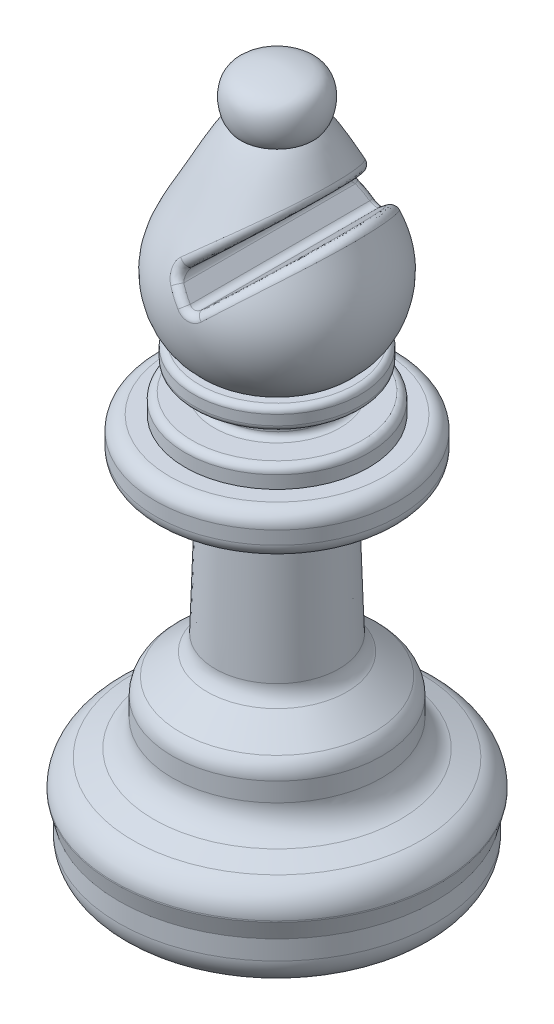
SolidWorks part; units mm, degrees
ref_plane "Front Plane" through (0, 0, 0) normal (0, 0, 1) x (1, 0, 0)
ref_plane "Top Plane" through (0, 0, 0) normal (0, 1, 0) x (1, 0, 0)
ref_plane "Right Plane" through (0, 0, 0) normal (1, 0, 0) x (0, 0, -1)
sketch "Sketch1" plane through (0, 0, 0) normal (0, 0, 1) x (1, 0, 0)
  line L0 (30.3333, 187) -> (151.6667, 187) construction
sketch "Sketch2" plane through (0, 0, 0) normal (0, 0, 1) x (1, 0, 0)
  line L0 (0, 0) -> (48.0183, 0) construction
  line L1 (24.0091, 0) -> (24.0091, 101.2767) construction
  line L2 (1.7406, 4) -> (1.7406, 6.7028)
  line L3 (1.7406, 6.7028) -> (1.1096, 9.1782)
  line L4 (1.1096, 9.1782) -> (1.1096, 9.3507)
  line L5 (3.7255, 13.1037) -> (6.6683, 14.1889)
  line L6 (5.7406, 0) -> (24.0091, 0)
  line L7 (9.2842, 17.9418) -> (9.2842, 20.5995)
  line L8 (10.4068, 22.9395) -> (14.1839, 25.9698)
  line L9 (15.305, 28.2161) -> (15.9553, 49.0232)
  line L10 (15.9553, 49.0232) -> (8.8895, 49.0232)
  line L11 (6.8895, 51.0232) -> (6.8895, 52.8811)
  line L12 (8.8895, 54.8811) -> (11.0789, 54.8811)
  line L13 (11.0789, 54.8811) -> (11.0789, 56.6558)
  line L14 (12.0789, 57.6558) -> (15.1553, 57.6558)
  line L15 (15.9553, 58.4558) -> (15.9553, 60.1747)
  line L16 (15.1553, 60.9747) -> (13.0731, 60.9747)
  line L17 (12.2731, 61.7747) -> (12.2731, 63.1671)
  line L18 (13.0731, 63.9671) -> (14.1142, 63.9671)
  line L19 (24.0091, 0) -> (24.0091, 97.4204)
  arc A0 (12.2731, 63.1671) -> (13.0731, 63.9671) centre (13.0731, 63.1671) cw
  arc A1 (13.0731, 60.9747) -> (12.2731, 61.7747) centre (13.0731, 61.7747) cw
  arc A2 (15.9553, 60.1747) -> (15.1553, 60.9747) centre (15.1553, 60.1747) ccw
  arc A3 (15.9553, 58.4558) -> (15.1553, 57.6558) centre (15.1553, 58.4558) cw
  arc A4 (11.0789, 56.6558) -> (12.0789, 57.6558) centre (12.0789, 56.6558) cw
  arc A5 (6.8895, 52.8811) -> (8.8895, 54.8811) centre (8.8895, 52.8811) cw
  arc A6 (8.8895, 49.0232) -> (6.8895, 51.0232) centre (8.8895, 51.0232) cw
  arc A7 (14.1839, 25.9698) -> (15.305, 28.2161) centre (12.3065, 28.3098) ccw
  arc A8 (9.2842, 20.5995) -> (10.4068, 22.9395) centre (12.2842, 20.5995) cw
  arc A9 (9.2842, 17.9418) -> (6.6683, 14.1889) centre (5.2842, 17.9418) cw
  arc A10 (1.1096, 9.3507) -> (3.7255, 13.1037) centre (5.1096, 9.3507) cw
  arc A11 (1.7406, 4) -> (5.7406, 0) centre (5.7406, 4) ccw
  spline S0 degree 3 poles (14.1142, 63.9671) (11.2688, 66.2111) (8.7669, 73.4376) (14.2158, 82.5039) (17.3181, 89.0028) (18.8934, 90.8018) knots 0 0 0 0 0.34709 0.628003 1 1 1 1
  spline S1 degree 3 poles (18.8934, 90.8018) (17.8856, 92.1232) (17.6169, 96.0792) (20.3351, 96.9141) (22.2755, 97.3387) (23.2424, 97.423) (24.0091, 97.4204) knots 0 0 0 0 0.50934 0.690884 0.73995 1 1 1 1
  point P54 (1.7406, 0)
  dimension "D1" = 0.8
  dimension "D2" = 0.8
  dimension "D3" = 0.8
  dimension "D4" = 0.8
  dimension "D5" = 1
  dimension "D6" = 2
  dimension "D7" = 2
  dimension "D8" = 3
  dimension "D9" = 3
  dimension "D10" = 4
  dimension "D11" = 4
  dimension "D12" = 4
revolve "Revolve1" add sketch "Sketch2" angle 360 about L19
sketch "Sketch4" plane through (0, 0, 0) normal (0, 0, 1) x (1, 0, 0)
  line L0 (37.0015, 90.5556) -> (22.2835, 77.1538)
  line L1 (22.2835, 77.1538) -> (25.0958, 74.0653)
  line L2 (25.0958, 74.0653) -> (39.8138, 87.4671)
  line L3 (39.8138, 87.4671) -> (37.0015, 90.5556)
extrude "Cut-Extrude1" cut sketch "Sketch4" against normal blind 22 and the other way blind 32
fillet "Fillet1" radius 1 6 edges at (32.0898, 86.0832, -0.1791) (34.0919, 82.2569, 0.8479) (22.2835, 77.1538, 0) (25.0958, 74.0653, 0)
